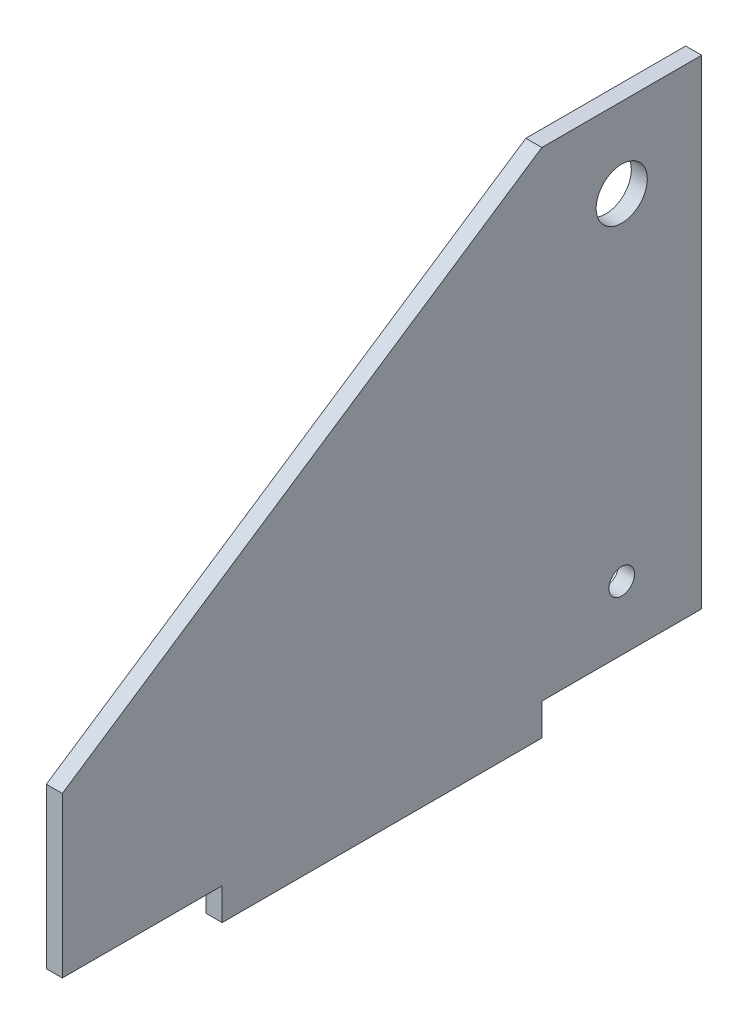
SolidWorks part; units mm, degrees
ref_plane "Alzado" through (0, 0, 0) normal (0, 0, 1) x (1, 0, 0)
ref_plane "Planta" through (0, 0, 0) normal (0, 1, 0) x (1, 0, 0)
ref_plane "Vista lateral" through (0, 0, 0) normal (1, 0, 0) x (0, 0, -1)
sketch "Croquis1" plane through (0, 0, 0) normal (1, 0, 0) x (0, 0, -1)
  line L0 (50, 75) -> (-100, -25)
  line L1 (-100, -75) -> (-50, -75)
  line L2 (-100, -75) -> (-100, -25)
  line L3 (50, 75) -> (100, 75)
  line L4 (100, -75) -> (100, 75)
  line L5 (100, 0) -> (-62.5, 0) construction
  line L6 (75, 75) -> (75, -75) construction
  line L7 (0, 41.6667) -> (0, -85) construction
  line L9 (-50, -75) -> (-50, -85)
  line L10 (-50, -85) -> (50, -85)
  line L11 (50, -75) -> (50, -85)
  line L14 (50, -75) -> (100, -75)
  circle A0 centre (75, 50) radius 8
  circle A1 centre (75, -55) radius 4
  point P0 (0, 0)
  point P13 (0, -75)
  dimension "D6" = 16
  dimension "D10" = 8
  dimension "D1" = 150
  dimension "D2" = 200
  dimension "D3" = 50
  dimension "D4" = 50
  dimension "D5" = 50
  dimension "D7" = 100
  dimension "D8" = 50
  dimension "D9" = 10
  dimension "D11" = 20
extrude "Saliente-Extruir1" add sketch "Croquis1" along normal blind 5
